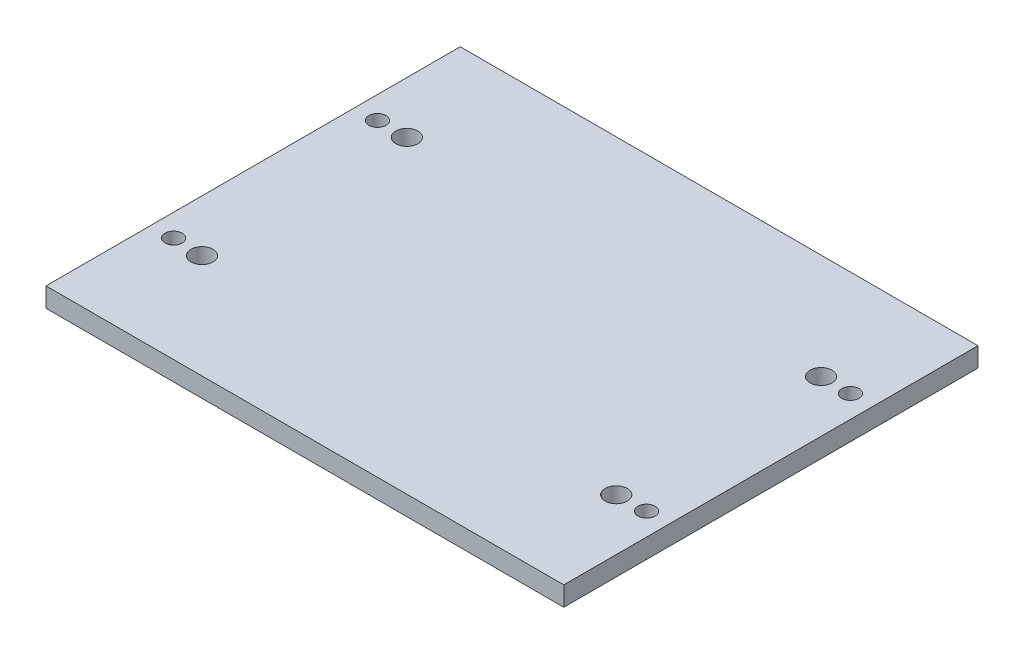
SolidWorks part; units mm, degrees
other "Markup1"
sketch "Sketch18" [suppressed] plane through (-63.5, -7.9375, -30) normal (-0.3676, -0.7619, -0.5334) x (0.8094, 0.0203, -0.5869)
ref_plane "Front Plane" through (0, 0, 0) normal (0, 0, 1) x (1, 0, 0)
ref_plane "Top Plane" through (0, 0, 0) normal (0, 1, 0) x (1, 0, 0)
ref_plane "Right Plane" through (0, 0, 0) normal (1, 0, 0) x (0, 0, -1)
sketch "Sketch1" plane through (0, 0, 0) normal (0, 1, 0) x (1, 0, 0)
  line L1 (-63.5, -50.8) -> (63.5, -50.8)
  line L2 (-63.5, -50.8) -> (-63.5, 50.8)
  line L3 (-63.5, 50.8) -> (63.5, 50.8)
  line L4 (63.5, -50.8) -> (63.5, 50.8)
  line L5 (-63.5, -50.8) -> (63.5, 50.8) construction
  line L6 (-63.5, 50.8) -> (63.5, -50.8) construction
  line L7 (58, 25) -> (-58, 25) construction
  line L8 (58, 25) -> (58, -25) construction
  line L9 (58, -25) -> (-58, -25) construction
  line L10 (-58, 25) -> (-58, -25) construction
  line L11 (58, 25) -> (-58, -25) construction
  line L12 (58, -25) -> (-58, 25) construction
  circle A0 centre (-58, 25) radius 2.75
  circle A1 centre (-58, -25) radius 2.75
  circle A2 centre (58, -25) radius 2.75
  circle A3 centre (58, 25) radius 2.75
  point P0 (0, 0)
  point P5 (0, 0)
  dimension "D5" = 5.5
  dimension "D1" = 101.6
  dimension "D2" = 127
  dimension "D3" = 50
  dimension "D4" = 116
extrude "Boss-Extrude1" add sketch "Sketch1" along normal blind 4.7625 contours A0 | L1 L4 L3 L2 A3 A2 A1 A0 | A1 | A2 | A3 region at (0, 0, 0) region at (-58, 0, -25) region at (-58, 0, 25) region at (58, 0, 25) region at (58, 0, -25)
sketch "Sketch2" plane through (0, 0, 0) normal (0, 1, 0) x (1, 0, 0)
  line L1 (-37.2297, 10.3476) -> (-31.88, -50.8)
  line L6 (37.2297, 10.3476) -> (31.88, -50.8)
  line L7 (-63.5, -50.8) -> (63.5, -50.8) construction
  line L11 (8.89, 41.275) -> (-8.89, 41.275)
  line L14 (-63.5, 50.8) -> (63.5, 50.8) construction
  arc A2 (37.2297, 10.3476) -> (8.89, 41.275) centre (8.89, 12.827) ccw
  arc A3 (-8.89, 41.275) -> (-37.2297, 10.3476) centre (-8.89, 12.827) ccw
  point P17 (0, 41.275)
  dimension "D1" = 9.525
  dimension "D2" = 28.448
  dimension "D3" = 95
  dimension "D4" = 17.78
sketch "Sketch7" plane through (0, 4.7625, 0) normal (0, 1, 0) x (1, 0, 0)
  point P0 (-58, 25)
  point P3 (58, 25)
  point P6 (58, -25)
  point P9 (-58, -25)
hole_wizard "M5x0.8 Tapped Hole1" positions "Sketch7" profile "Sketch8" tap size "M5x0.8" standard "ANSI Metric" end condition through all
sketch "Sketch8" plane through (-58, 4.7625, -25) normal (1, 0, 0) x (0, 0, 1)
  line L0 (0, 0) -> (0, 4.7625)
  line L1 (0, 4.7625) -> (2.1, 4.7625)
  line L2 (2.1, 4.7625) -> (2.1, 0)
  line L5 (2.1, 0) -> (0, 0)
  line L11 (0, -6.35) -> (0, 107.95) construction
  dimension "Thru Tap Drill Dia." = 4.2
  dimension "Thru Tap Drill Depth" = 4.7625
cosmetic thread "Hole Thread1" parameters "D2"=5
cosmetic thread "Hole Thread2" parameters "D2"=5
cosmetic thread "Hole Thread3" parameters "D2"=5
cosmetic thread "Hole Thread4" parameters "D2"=5
sketch "Sketch11" plane through (0, 0, 0) normal (0, -1, 0) x (-1, 0, 0)
  line L0 (0, 50.8) -> (0, -50.8) construction
  line L1 (63.5, 50.8) -> (-63.5, 50.8) construction
  line L2 (63.5, -50.8) -> (-63.5, -50.8) construction
  point P0 (-50.8, 25)
  point P2 (50.8, 25)
  point P4 (50.8, -25.2375)
  point P6 (-50.8, -25.2375)
  point P60 (0, 0)
  dimension "D1" = 101.6
  dimension "D2" = 50.2375
hole_wizard "1/4-28 Tapped Hole1" positions "Sketch11" profile "Sketch12" tap size "1/4-28" standard "ANSI Inch" end condition through all
sketch "Sketch12" plane through (50.8, 0, -25) normal (1, 0, 0) x (0, 0, -1)
  line L0 (0, 0) -> (0, 4.7625)
  line L1 (0, 4.7625) -> (2.7051, 4.7625)
  line L2 (2.7051, 4.7625) -> (2.7051, 0)
  line L5 (2.7051, 0) -> (0, 0)
  line L11 (0, -6.35) -> (0, 107.95) construction
  dimension "Thru Tap Drill Dia." = 5.4102
  dimension "Thru Tap Drill Depth" = 4.7625
cosmetic thread "Hole Thread5" parameters "D2"=6.35
cosmetic thread "Hole Thread6" parameters "D2"=6.35
cosmetic thread "Hole Thread7" parameters "D2"=6.35
cosmetic thread "Hole Thread8" parameters "D2"=6.35
sketch "Sketch19" [suppressed] plane through (0, 0, 0) normal (0, -1, 0) x (1, 0, 0)
  circle A0 centre (-50.8, 25.2375) radius 3.2639
  circle A1 centre (50.8, 25.2375) radius 3.2639
  circle A2 centre (50.8, -25) radius 3.2639
  circle A3 centre (-50.8, -25) radius 3.2639
  dimension "D1" = 6.5278
extrude "Cut-Extrude5" [suppressed] cut sketch "Sketch19" against normal through all
sketch "Sketch26" [suppressed] plane through (0, 0, 50.8) normal (0, 0, 1) x (1, 0, 0)
  line L0 (27.1175, 0) -> (36.6425, 0)
  line L2 (36.6425, 0) -> (36.6425, 1.5875)
  line L3 (27.1175, 1.5875) -> (27.1175, 0)
  line L4 (-63.5, 0) -> (63.5, 0) construction
  arc A0 (36.6425, 1.5875) -> (27.1175, 1.5875) centre (31.88, 1.5875) ccw
  point P9 (31.88, 0)
  dimension "D3" = 4.7625
  dimension "D2" = 1.5875
sweep "Cut-Sweep9" [suppressed] cut profiles "Sketch26" path "Sketch2"
sketch "Sketch27" [suppressed] plane through (0, 0, 0) normal (0, -1, 0) x (1, 0, 0)
  line L0 (-23.293, 50.8) -> (-28.7079, -11.0932)
  line L1 (-27.1175, 50.8) -> (27.1175, 50.8) construction
  line L2 (-8.89, -32.7206) -> (8.89, -32.7206)
  line L3 (28.7079, -11.0932) -> (23.293, 50.8)
  line L5 (-23.293, 50.8) -> (23.293, 50.8)
  line L6 (40.4671, 50.8) -> (41.8919, 34.5138)
  line L7 (36.6425, 50.8) -> (63.5, 50.8) construction
  line L9 (-63.5, -50.8) -> (63.5, -50.8) construction
  line L10 (36.6425, 50.8) -> (41.9922, -10.3476) construction
  line L11 (-40.4671, 50.8) -> (-41.8919, 34.5138)
  line L12 (-63.5, 50.8) -> (-36.6425, 50.8) construction
  line L14 (-63.5, -50.8) -> (63.5, -50.8) construction
  line L15 (-41.9199, -9.5206) -> (-36.6425, 50.8) construction
  line L16 (-40.4671, 50.8) -> (-63.5, 50.8)
  line L17 (-63.5, 50.8) -> (-63.5, -50.8)
  line L18 (-63.5, -50.8) -> (-8.89, -50.8)
  line L19 (8.89, -50.8) -> (63.5, -50.8)
  line L20 (63.5, -50.8) -> (63.5, 50.8)
  line L21 (63.5, 50.8) -> (40.4671, 50.8)
  line L22 (27.1175, 50.8) -> (32.4672, -10.3476) construction
  line L23 (-37.2297, -10.3476) -> (-31.88, 50.8) construction
  line L24 (-43.6381, 14.5552) -> (-45.7516, -9.602)
  line L25 (43.6381, 14.5552) -> (45.7516, -9.602)
  arc A0 (-28.7079, -11.0932) -> (-8.89, -32.7206) centre (-8.89, -12.827) ccw
  arc A1 (8.89, -32.7206) -> (28.7079, -11.0932) centre (8.89, -12.827) ccw
  arc A2 (-37.2297, -10.3476) -> (-8.89, -41.275) centre (-8.89, -12.827) ccw construction
  arc A3 (8.89, -41.275) -> (37.2297, -10.3476) centre (8.89, -12.827) ccw construction
  arc A4 (41.8919, 34.5138) -> (47.4771, 31.4824) centre (45.6874, 34.8459) ccw
  arc A5 (47.4771, 31.4824) -> (48.612, 18.5105) centre (50.8, 25.2375) cw
  arc A6 (48.612, 18.5105) -> (43.6381, 14.5552) centre (47.4336, 14.8873) ccw
  arc A7 (45.8722, -14.0481) -> (50.0722, -17.9636) centre (49.6801, -14.1739) ccw
  arc A8 (50.0722, -17.9636) -> (46.9301, -30.9215) centre (50.8, -25) cw
  arc A9 (46.9301, -30.9215) -> (41.5671, -32.17) centre (44.8458, -34.1108) ccw
  arc A10 (41.5671, -32.17) -> (8.89, -50.8) centre (8.89, -12.827) cw
  circle A11 centre (50.8, -25) radius 3.2639 construction
  circle A12 centre (50.8, 25.2375) radius 3.2639 construction
  arc A14 (8.4749, -46.0194) -> (41.9922, -10.3476) centre (8.89, -12.827) ccw construction
  arc A15 (-41.8919, 34.5138) -> (-47.4771, 31.4824) centre (-45.6874, 34.8459) cw
  arc A16 (-47.4771, 31.4824) -> (-48.612, 18.5105) centre (-50.8, 25.2375) ccw
  arc A17 (-48.612, 18.5105) -> (-43.6381, 14.5552) centre (-47.4336, 14.8873) cw
  arc A18 (-45.8722, -14.0481) -> (-50.0722, -17.9636) centre (-49.6801, -14.1739) cw
  arc A19 (-50.0722, -17.9636) -> (-46.9301, -30.9215) centre (-50.8, -25) ccw
  arc A20 (-46.9301, -30.9215) -> (-41.5671, -32.17) centre (-44.8458, -34.1108) cw
  arc A21 (-41.5671, -32.17) -> (-8.89, -50.8) centre (-8.89, -12.827) ccw
  circle A22 centre (-50.8, -25) radius 3.2639 construction
  circle A23 centre (-50.8, 25.2375) radius 3.2639 construction
  arc A24 (-41.9199, -9.5206) -> (-9.3051, -46.0194) centre (-8.89, -12.827) ccw construction
  arc A25 (-45.7516, -9.602) -> (-45.8722, -14.0481) centre (-8.89, -12.827) ccw
  arc A26 (45.7516, -9.602) -> (45.8722, -14.0481) centre (8.89, -12.827) cw
  dimension "D4" = 3.81
  dimension "D2" = 3.81
  dimension "D3" = 3.81
  dimension "D5" = 3.81
  dimension "D6" = 3.81
  dimension "D7" = 3.81
  dimension "D8" = 3.81
  dimension "D1" = 3.81
extrude "Cut-Extrude6" [suppressed] cut sketch "Sketch27" against normal blind 6.35
sketch "Sketch28" [suppressed] plane through (0, 0, 0) normal (0, -1, 0) x (-1, 0, 0)
  line L0 (41.8919, -34.5138) -> (43.6381, -14.5552)
  line L1 (-41.8919, -34.5138) -> (-43.6381, -14.5552)
  arc A0 (45.8722, 14.0481) -> (41.5671, 32.17) centre (-0.9264, 12.5029) ccw
  arc A1 (46.9301, 30.9215) -> (41.5671, 32.17) centre (44.8458, 34.1108) cw
  arc A2 (45.7516, 9.602) -> (45.8722, 14.0481) centre (8.89, 12.827) ccw construction
  arc A3 (45.8722, 14.0481) -> (50.0722, 17.9636) centre (49.6801, 14.1739) cw
  arc A4 (50.0722, 17.9636) -> (45.8722, 14.0481) centre (49.6801, 14.1739) ccw construction
  arc A5 (50.0722, 17.9636) -> (46.9301, 30.9215) centre (50.8, 25) ccw
  arc A6 (47.4771, -31.4824) -> (48.612, -18.5105) centre (50.8, -25.2375) ccw
  arc A7 (48.612, -18.5105) -> (43.6381, -14.5552) centre (47.4336, -14.8873) cw
  arc A8 (47.4771, -31.4824) -> (41.8919, -34.5138) centre (45.6874, -34.8459) ccw
  arc A9 (-41.8919, -34.5138) -> (-47.4771, -31.4824) centre (-45.6874, -34.8459) ccw
  arc A10 (-43.6381, -14.5552) -> (-48.612, -18.5105) centre (-47.4336, -14.8873) cw
  arc A11 (-45.8722, 14.0481) -> (-50.0722, 17.9636) centre (-49.6801, 14.1739) ccw
  arc A12 (-41.5671, 32.17) -> (-46.9301, 30.9215) centre (-44.8458, 34.1108) cw
  arc A13 (-46.9301, 30.9215) -> (-50.0722, 17.9636) centre (-50.8, 25) ccw
  arc A14 (-48.612, -18.5105) -> (-47.4771, -31.4824) centre (-50.8, -25.2375) ccw
  arc A15 (47.4771, -31.4824) -> (48.612, -18.5105) centre (50.8, -25.2375) ccw construction
  arc A16 (-48.612, -18.5105) -> (-47.4771, -31.4824) centre (-50.8, -25.2375) ccw construction
  arc A17 (-46.9301, 30.9215) -> (-50.0722, 17.9636) centre (-50.8, 25) ccw construction
  arc A18 (-45.8722, 14.0481) -> (-41.5671, 32.17) centre (0.9264, 12.5029) cw
  arc A19 (-8.89, 41.275) -> (-37.2297, 10.3476) centre (-8.89, 12.827) ccw construction
  arc A20 (-45.8722, 14.0481) -> (-45.7516, 9.602) centre (-8.89, 12.827) ccw construction
  dimension "D1" = 28.1978
extrude "Cut-Extrude7" [suppressed] cut sketch "Sketch28" against normal blind 3.175
fillet "Fillet1" [suppressed] radius 3.048
fillet "Fillet2" [suppressed] radius 3.175
equation "\"D3@Sketch27\"=\"D2@Sketch27\""
equation "\"D5@Sketch27\"=\"D2@Sketch27\""
equation "\"D4@Sketch27\"=\"D2@Sketch27\""
equation "\"D6@Sketch27\"=\"D2@Sketch27\""
equation "\"D7@Sketch27\"=\"D2@Sketch27\""
equation "\"D8@Sketch27\"=\"D2@Sketch27\""
equation "\"D1@Sketch27\"=\"D2@Sketch27\""
